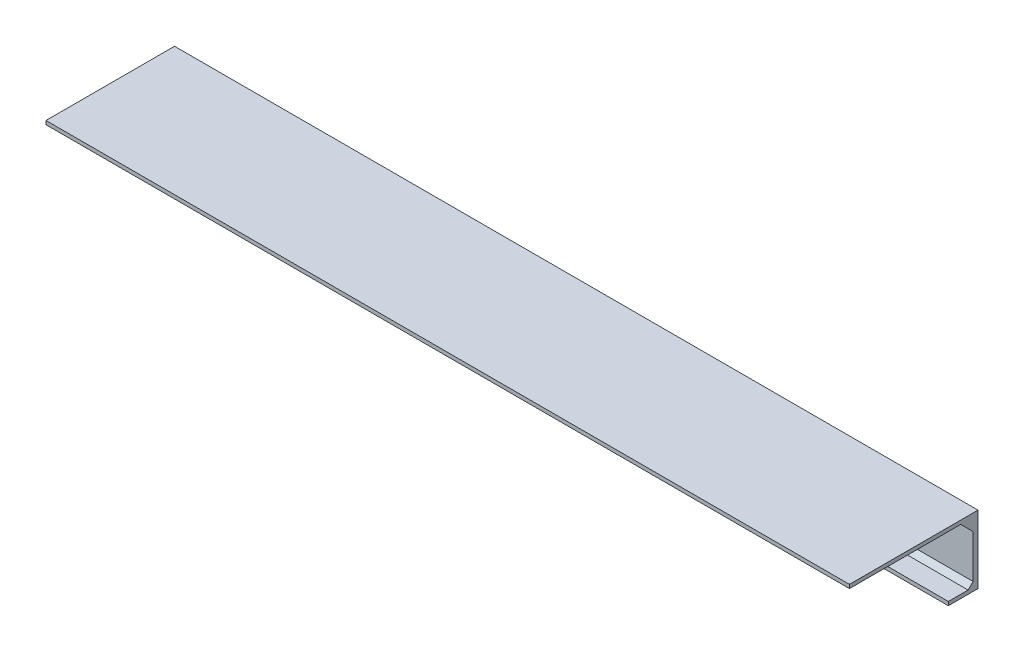
SolidWorks part; units mm, degrees
ref_plane "前视基准面" through (0, 0, 0) normal (0, 0, 1) x (1, 0, 0)
ref_plane "上视基准面" through (0, 0, 0) normal (0, 1, 0) x (1, 0, 0)
ref_plane "右视基准面" through (0, 0, 0) normal (1, 0, 0) x (0, 0, -1)
sketch "草图1" plane through (0, 0, 0) normal (0, 0, 1) x (1, 0, 0)
  line L1 (65, -5.5) -> (-65, -5.5)
  line L2 (65, -5.5) -> (65, 5.5)
  line L3 (65, 5.5) -> (-65, 5.5)
  line L4 (-65, -5.5) -> (-65, 5.5)
  line L5 (65, -5.5) -> (-65, 5.5) construction
  line L6 (65, 5.5) -> (-65, -5.5) construction
  point P0 (0, 0)
  dimension "D1" = 130
  dimension "D2" = 11
extrude "凸台-拉伸1" add sketch "草图1" along normal blind 0.8
sketch "草图2" plane through (0, 0, 0.8) normal (0, 0, 1) x (1, 0, 0)
  line L0 (65, -5.5) -> (65, 5.5) construction
  line L1 (-65, 5.5) -> (65, 5.5)
  line L2 (-65, 5.5) -> (-65, 4.9)
  line L3 (-65, 4.9) -> (65, 4.9)
  line L4 (65, 5.5) -> (65, 4.9)
  dimension "D1" = 0.6
extrude "凸台-拉伸2" add sketch "草图2" along normal blind 20
sketch "草图3" plane through (0, 0, 0.8) normal (0, 0, 1) x (1, 0, 0)
  line L0 (65, -5.5) -> (65, 4.9) construction
  line L1 (-65, 4.9) -> (65, 4.9)
  line L2 (-65, 4.9) -> (-65, 2.9)
  line L3 (-65, 2.9) -> (65, 2.9)
  line L4 (65, 4.9) -> (65, 2.9)
  dimension "D1" = 2
extrude "凸台-拉伸3" add sketch "草图3" along normal blind 2
chamfer "倒角1" distance 2 angle 45 1 edges at (0, 2.9, 2.8)
sketch "草图4" plane through (0, 0, 0.8) normal (0, 0, 1) x (1, 0, 0)
  line L0 (65, -5.5) -> (65, 2.9) construction
  line L1 (-65, -5.5) -> (65, -5.5)
  line L2 (-65, -5.5) -> (-65, -4.9)
  line L3 (-65, -4.9) -> (65, -4.9)
  line L4 (65, -5.5) -> (65, -4.9)
  dimension "D1" = 0.6
extrude "凸台-拉伸4" add sketch "草图4" along normal blind 4
sketch "草图5" plane through (0, 0, 0.8) normal (0, 0, 1) x (1, 0, 0)
  line L0 (65, -4.9) -> (65, 2.9) construction
  line L1 (-65, -4.9) -> (65, -4.9)
  line L2 (-65, -4.9) -> (-65, -4.1)
  line L3 (-65, -4.1) -> (65, -4.1)
  line L4 (65, -4.9) -> (65, -4.1)
  dimension "D1" = 0.8
extrude "凸台-拉伸5" add sketch "草图5" along normal blind 0.8
chamfer "倒角2" distance 0.8 angle 45 1 edges at (0, -4.1, 1.6)
